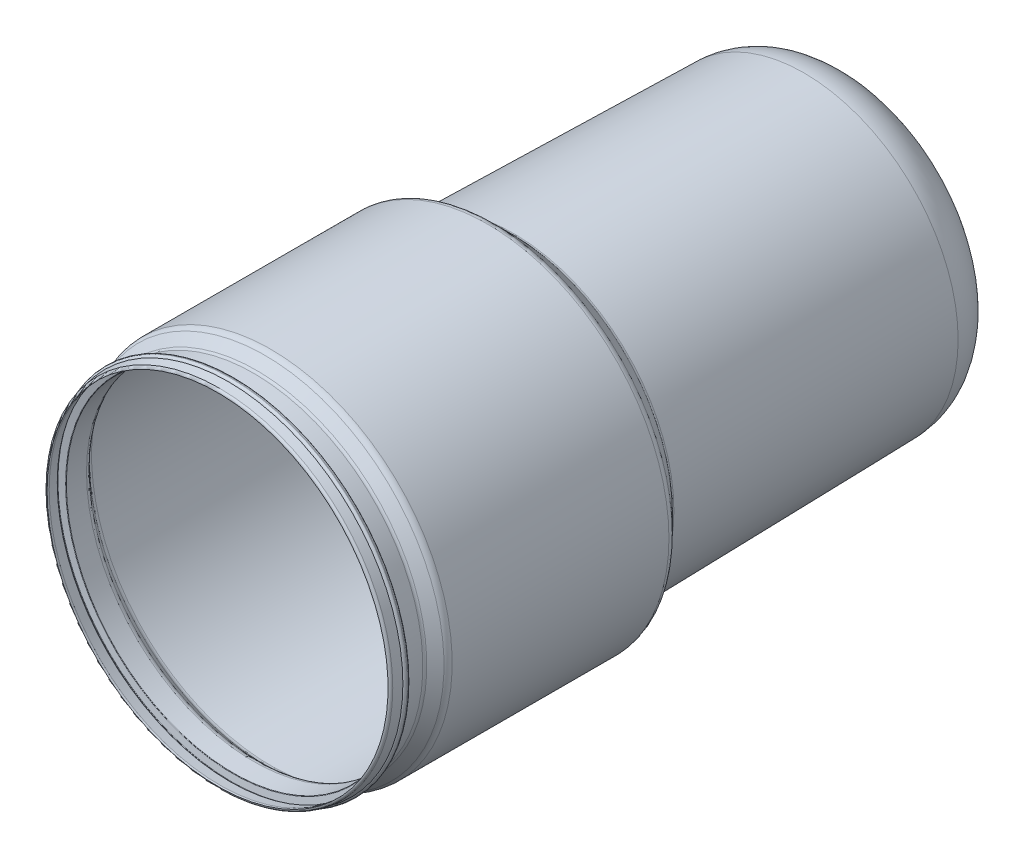
SolidWorks part; units mm, degrees
ref_plane "Front Plane" through (0, 0, 0) normal (1, 0, 0) x (0, 1, 0)
ref_plane "Top Plane" through (0, 0, 0) normal (0, 0, 1) x (0, 1, 0)
ref_plane "Right Plane" through (0, 0, 0) normal (0, 1, 0) x (-1, 0, 0)
sketch "Sketch1" plane through (0, 0, 0) normal (0, 1, 0) x (-1, 0, 0)
  line L0 (0, 0) -> (0, 660.4) construction
  line L1 (0, 0) -> (-107.9609, 0)
  line L2 (-158.75, 49.7455) -> (-165.1, 355.6)
  line L3 (0, 0) -> (0, 660.4)
  line L4 (-165.1, 355.6) -> (-187.325, 377.825)
  line L5 (-187.325, 377.825) -> (-187.325, 609.6)
  line L6 (-187.325, 609.6) -> (-174.625, 622.3)
  line L7 (-174.625, 622.3) -> (-174.625, 646.3748)
  line L8 (-174.625, 646.3748) -> (-182.1407, 647.7)
  line L9 (-178.5938, 660.4) -> (0, 660.4)
  line L10 (-182.1407, 647.7) -> (-182.1407, 649.2875)
  line L11 (-182.1407, 649.2875) -> (-180.5532, 649.2875)
  line L12 (-180.5532, 649.2875) -> (-178.5938, 660.4)
  arc A0 (-107.9609, 0) -> (-158.75, 49.7455) centre (-107.9609, 50.8) cw
  point P3 (-289.7715, 660.4)
  point P10 (-187.325, 270.6644)
  point P11 (-158.75, 119.798)
  point P17 (-249.46, 160.0983)
  point P18 (-299.0417, 494.94)
  point P19 (-267.567, 472.2782)
  point P20 (-263.79, 425.6956)
  point P21 (-285.7302, 418.1417)
  point P22 (-285.1928, 367.7822)
  point P23 (-243.6462, 319.9406)
  point P25 (-208.3946, 254.4732)
  point P26 (-248.6822, 364.0052)
  point P27 (-211.2119, 554.7905)
  point P28 (-240.7466, 519.9546)
  point P29 (-246.0477, 430.593)
  point P30 (-177.7452, 237.1972)
  point P31 (-165.1, 232.1043)
  point P32 (-165.1, 237.1972)
  point P33 (-187.325, 382.8094)
  point P34 (-177.951, 610.1752)
  point P35 (-174.625, 582.5962)
  point P36 (-174.625, 611.2674)
  point P37 (-203.6975, 651.4039)
  point P38 (-174.625, 646.3129)
  point P39 (-179.3145, 655.8213)
  point P40 (-181.7223, 647.7)
  dimension "D1" = 50.8
  dimension "D2" = 158.75
  dimension "D3" = 660.4
  dimension "D4" = 165.1
  dimension "D5" = 187.325
  dimension "D6" = 355.6
  dimension "D7" = 45
  dimension "D8" = 45
  dimension "D9" = 174.625
  dimension "D10" = 38.1
  dimension "D11" = 178.5938
  dimension "D12" = 100
  dimension "D13" = 1.5875
  dimension "D14" = 12.7
  dimension "D15" = 1.5875
  dimension "D16" = 100
revolve "Revolve1" add sketch "Sketch1" angle 360 about L0
fillet "Fillet1" radius 6.35 4 edges at (-165.1, 0, 355.6) (-187.325, 0, 377.825) (-187.325, 0, 609.6) (-174.625, 0, 622.3)
fillet "Fillet2" radius 0.508 5 edges at (-178.5938, 0, 660.4) (-180.5532, 0, 649.2875) (-182.1407, 0, 649.2875) (-182.1407, 0, 647.7) (-174.625, 0, 646.3748)
shell "Shell1" thickness 2.2 removed face at (-178.1675, 0, 660.4) outward yes
